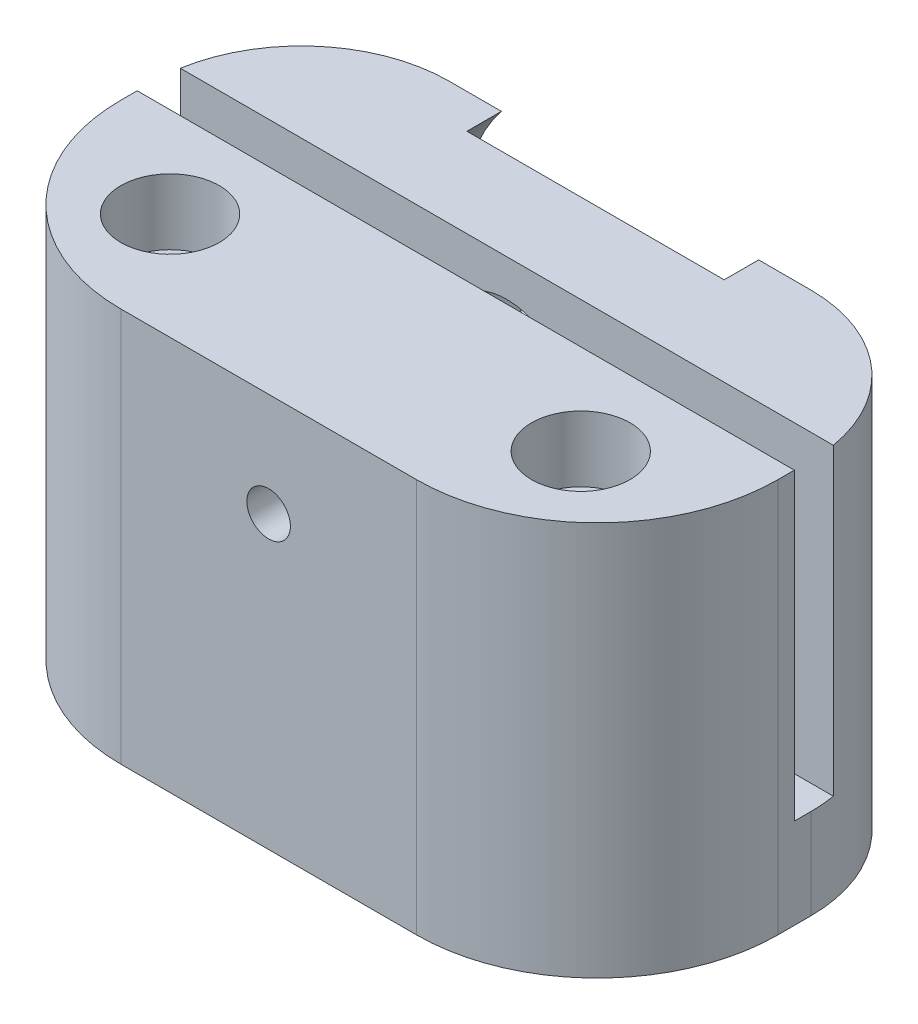
SolidWorks part; units mm, degrees
material "ABS"
ref_plane "Front Plane" through (0, 0, 0) normal (0, 0, 1) x (1, 0, 0)
ref_plane "Top Plane" through (0, 0, 0) normal (0, 1, 0) x (1, 0, 0)
ref_plane "Right Plane" through (0, 0, 0) normal (1, 0, 0) x (0, 0, -1)
sketch "Sketch2" plane through (0, 0, 0) normal (0, 1, 0) x (1, 0, 0)
  line L1 (0, 0) -> (40, 0)
  line L2 (0, 0) -> (0, 12)
  line L3 (0, 12) -> (40, 12)
  line L4 (40, 0) -> (40, 12)
  dimension "D1" = 40
  dimension "D2" = 12
extrude "Boss-Extrude1" add sketch "Sketch2" along normal blind 24
hole_wizard "CBORE for M2.5 Hex Head Machine Screw1" positions "Sketch8" profile "Sketch9" counterbore size "M2.5" standard "ANSI Metric"
sketch "Sketch8" plane through (0, 24, 0) normal (0, 1, 0) x (1, 0, 0)
  line L4 (0, 12) -> (0, 0) construction
  line L5 (40, 12) -> (0, 12) construction
  point P0 (7.5, 6.5)
  point P2 (32.5, 6.5)
  dimension "D1" = 5.5
  dimension "D2" = 25
  dimension "D3" = 5.5
  dimension "D4" = 7.5
sketch "Sketch9" plane through (7.5, 24, -6.5) normal (1, 0, 0) x (0, 0, 1)
  line L0 (0, 0) -> (0, 39.0013)
  line L1 (0, 39.0013) -> (1.5, 38.1)
  line L2 (1.5, 38.1) -> (1.5, 4)
  line L3 (1.5, 4) -> (3, 4)
  line L4 (3, 4) -> (3, 0)
  line L5 (3, 0) -> (0, 0)
  line L10 (0, 39.0013) -> (-1.5, 38.1) construction
  line L11 (0, -6.35) -> (0, 107.95) construction
  dimension "Hole Dia." = 3
  dimension "Hole Depth" = 38.1
  dimension "C'Bore Dia." = 6
  dimension "C'Bore Depth" = 4
  dimension "Drill Angle" = 118
sketch "Sketch11" plane through (0, 0, -12) normal (0, 0, -1) x (-1, 0, 0)
  line L0 (0, 24) -> (0, 0) construction
  line L1 (-40, 0) -> (0, 0)
  line L2 (-40, 0) -> (-40, 5.5)
  line L3 (-40, 5.5) -> (0, 5.5)
  line L4 (0, 0) -> (0, 5.5)
  dimension "D1" = 5.5
extrude "Boss-Extrude2" add sketch "Sketch11" along normal blind 10
sketch "Sketch12" plane through (0, 5.5, 0) normal (0, 1, 0) x (1, 0, 0)
  line L0 (40, 22) -> (40, 12) construction
  line L1 (40, 14.5) -> (0, 14.5)
  line L2 (40, 14.5) -> (40, 22)
  line L3 (40, 22) -> (0, 22)
  line L4 (0, 14.5) -> (0, 22)
  dimension "D1" = 7.5
extrude "Boss-Extrude3" add sketch "Sketch12" along normal blind 18.5
sketch "Sketch10" plane through (0, 0, -12) normal (0, 0, -1) x (-1, 0, 0)
  line L0 (-40, 24) -> (-40, 5.5) construction
  line L1 (-40, 0) -> (0, 0) construction
  circle A0 centre (-20, 17.7) radius 4.05
  dimension "D1" = 20
  dimension "D3" = 8.1
  dimension "D2" = 17.7
extrude "Cut-Extrude1" cut sketch "Sketch10" against normal blind 6 and the other way blind 17
sketch "Sketch13" plane through (0, 0, -22) normal (0, 0, -1) x (-1, 0, 0)
  circle A0 centre (-20, 17.7) radius 4.8
  dimension "D1" = 9.6
extrude "Cut-Extrude2" cut sketch "Sketch13" against normal blind 5.5
sketch "Sketch14" plane through (0, 0, -22) normal (0, 0, -1) x (-1, 0, 0)
  circle A0 centre (-20, 17.7) radius 10.05
  dimension "D1" = 20.1
extrude "Cut-Extrude3" cut sketch "Sketch14" against normal blind 2.1
hole_wizard "Tap Drill for M2.5 Helicoil1" positions "Sketch15" profile "Sketch16" hole size "M2.5x0.45" standard "ANSI Metric" end condition through all
sketch "Sketch15" plane through (0, 0, -6) normal (0, 0, -1) x (-1, 0, 0)
  point P0 (-20, 17.7)
sketch "Sketch16" plane through (20, 17.7, -6) normal (1, 0, 0) x (0, 1, 0)
  line L0 (0, 0) -> (0, 6)
  line L1 (0, 6) -> (1.325, 6)
  line L2 (1.325, 6) -> (1.325, 0)
  line L5 (1.325, 0) -> (0, 0)
  line L11 (0, -6.35) -> (0, 107.95) construction
  dimension "Thru Hole Dia." = 2.65
  dimension "Thru Hole Depth" = 6
fillet "Fillet1" radius 11 2 edges at (0, 12, 0) (40, 12, 0)
fillet "Fillet2" radius 9 2 edges at (0, 12, -22) (40, 12, -22)
